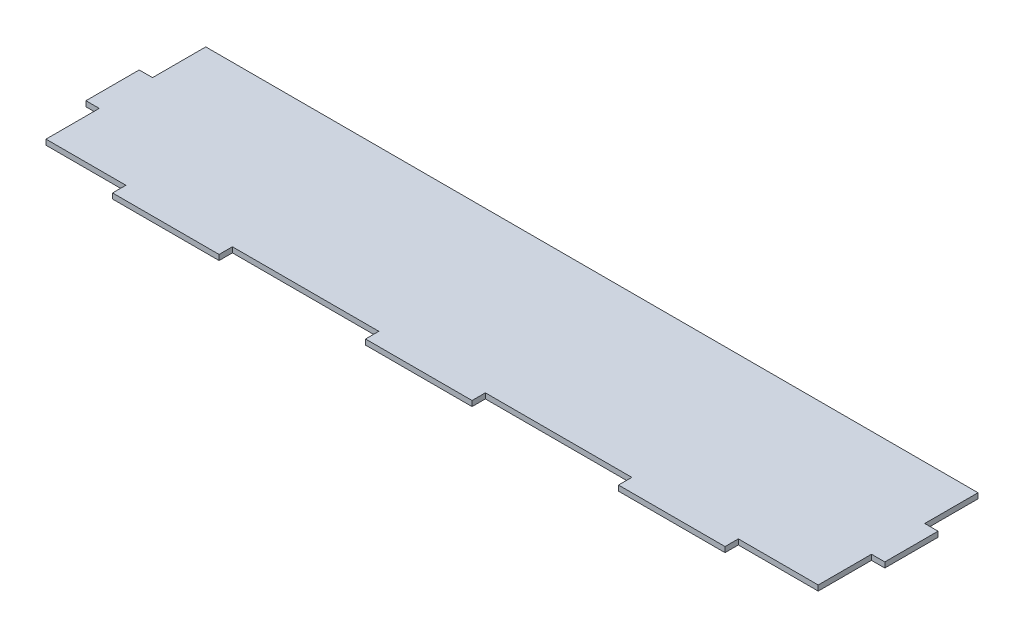
SolidWorks part; units mm, degrees
ref_plane "Front Plane" through (0, 0, 0) normal (0, 0, 1) x (1, 0, 0)
ref_plane "Top Plane" through (0, 0, 0) normal (0, 1, 0) x (1, 0, 0)
ref_plane "Right Plane" through (0, 0, 0) normal (1, 0, 0) x (0, 0, -1)
sketch "Sketch1" plane through (0, 0, 0) normal (0, 1, 0) x (1, 0, 0)
  line L0 (0, 12.434) -> (0, -12.966)
  line L1 (6.35, 37.834) -> (374.65, 37.834)
  line L2 (381, 12.434) -> (381, -12.966)
  line L3 (6.35, -38.366) -> (44.45, -38.366)
  line L4 (95.25, -38.366) -> (165.1, -38.366)
  line L5 (165.1, -38.366) -> (165.105, -38.311)
  line L7 (0, 12.434) -> (6.35, 12.434)
  line L8 (6.35, 37.834) -> (6.35, 12.434)
  line L9 (44.45, -38.366) -> (44.45, -44.716)
  line L11 (0, -12.966) -> (6.35, -12.966)
  line L12 (6.35, -38.366) -> (6.35, -12.966)
  line L14 (381, 12.434) -> (374.65, 12.434)
  line L15 (374.65, 37.834) -> (374.65, 12.434)
  line L16 (44.45, -44.716) -> (95.25, -44.716)
  line L17 (95.25, -38.366) -> (95.25, -44.716)
  line L18 (381, -12.966) -> (374.65, -12.966)
  line L19 (374.65, -38.366) -> (374.65, -12.966)
  line L20 (215.9, -38.366) -> (285.75, -38.366)
  line L21 (336.55, -38.366) -> (336.55, -44.716)
  line L22 (336.55, -44.716) -> (285.75, -44.716)
  line L23 (285.75, -38.366) -> (285.75, -44.716)
  line L24 (336.55, -38.366) -> (374.65, -38.366)
  line L25 (165.1, -38.366) -> (165.1, -44.716)
  line L26 (165.1, -44.716) -> (215.9, -44.716)
  line L27 (215.9, -38.366) -> (215.9, -44.716)
  dimension "D2" = 368.3
  dimension "D3" = 25.4
  dimension "D4" = 25.4
  dimension "D5" = 6.35
  dimension "D6" = 6.35
  dimension "D7" = 25.4
  dimension "D8" = 25.4
  dimension "D9" = 25.4
  dimension "D10" = 6.35
  dimension "D11" = 6.35
  dimension "D12" = 6.35
  dimension "D13" = 368.3
  dimension "D14" = 6.35
  dimension "D15" = 25.4
  dimension "D16" = 25.4
  dimension "D17" = 25.4
  dimension "D18" = 25.4
  dimension "D19" = 25.4
  dimension "D20" = 50.8
  dimension "D21" = 25.4
  dimension "D22" = 69.85
  dimension "D23" = 6.35
  dimension "D24" = 50.8
  dimension "D25" = 44.45
  dimension "D26" = 6.35
  dimension "D27" = 50.8
  dimension "D28" = 44.45
  dimension "D29" = 6.35
  dimension "D30" = 50.8
  dimension "D31" = 69.85
  dimension "D32" = 69.85
  dimension "D33" = 50.8
  dimension "D34" = 50.8
  dimension "D35" = 38.1
  dimension "D36" = 6.35
  dimension "D37" = 6.35
  dimension "D38" = 6.35
  dimension "D39" = 6.35
extrude "Boss-Extrude1" add sketch "Sketch1" along normal blind 2.54 contours L27 L20 L23 L22 L21 L24 L19 L18 L2 L14 L15 L1 L8 L7 L0 L11 L12 L3 L9 L16 L17 L4 L25 L26 region at (190.5, 0, 1.6267)
shell "Shell1" thickness 0.1016
